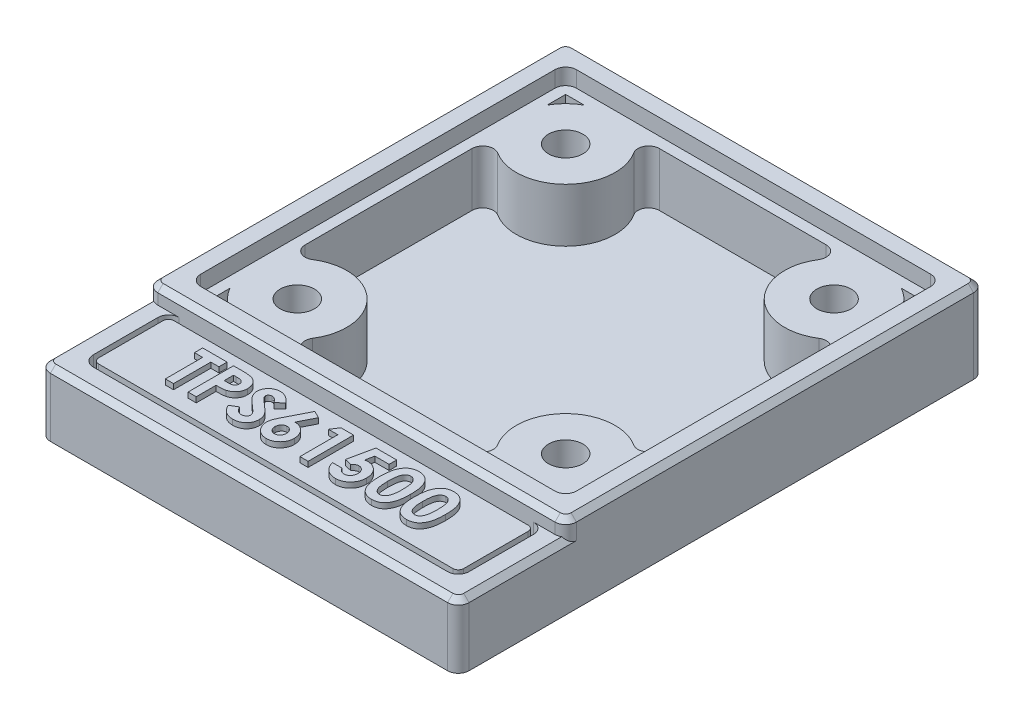
SolidWorks part; units mm, degrees
other "Markup1"
sketch "Sketch7" plane through (-28, 7.5, 62.5) normal (-0.8225, 0.3134, 0.4747) x (0.5688, 0.4607, 0.6813)
material "PET"
ref_plane "Front Plane" through (0, 0, 0) normal (0, 0, 1) x (1, 0, 0)
ref_plane "Top Plane" through (0, 0, 0) normal (0, 1, 0) x (1, 0, 0)
ref_plane "Right Plane" through (0, 0, 0) normal (1, 0, 0) x (0, 0, -1)
sketch "base_sketch" plane through (0, 0, 0) normal (0, 1, 0) x (1, 0, 0)
  line L1 (-12.5, 12.5) -> (12.5, 12.5) construction
  line L2 (-12.5, 12.5) -> (-12.5, -12.5) construction
  line L3 (-12.5, -12.5) -> (12.5, -12.5) construction
  line L4 (12.5, 12.5) -> (12.5, -12.5) construction
  line L5 (-12.5, 12.5) -> (12.5, -12.5) construction
  line L6 (-12.5, -12.5) -> (12.5, 12.5) construction
  line L7 (-17, 17) -> (17, 17) construction
  line L8 (-17, 17) -> (-17, -17) construction
  line L9 (-17, -17) -> (17, -17) construction
  line L10 (17, 17) -> (17, -17) construction
  line L11 (-17, 17) -> (17, -17) construction
  line L12 (-17, -17) -> (17, 17) construction
  circle A0 centre (-12.5, 12.5) radius 1.6 construction
  circle A1 centre (12.5, 12.5) radius 1.6 construction
  circle A2 centre (-12.5, -12.5) radius 1.6 construction
  circle A3 centre (12.5, -12.5) radius 1.6 construction
  point P0 (0, 0)
  point P11 (0, 0)
  dimension "D1" = 3.2
  dimension "D2" = 25
  dimension "D3" = 34
  dimension "D4" = 34
  dimension "D5" = 25
sketch "Sketch3" plane through (0, 0, 0) normal (0, 1, 0) x (1, 0, 0)
  line L14 (-16.5, -16.5) -> (16.5, -16.5)
  line L15 (16.5, -16.5) -> (16.5, 16.5)
  line L16 (16.5, 16.5) -> (-16.5, 16.5)
  line L17 (-16.5, 16.5) -> (-16.5, -16.5)
  line L18 (-16.5, -16.5) -> (16.5, -16.5)
  line L19 (16.5, -16.5) -> (16.5, 16.5)
  line L20 (16.5, 16.5) -> (-16.5, 16.5)
  line L21 (-16.5, 16.5) -> (-16.5, -16.5)
  line L28 (-19.5, 19.5) -> (-19.5, -19.5)
  line L29 (-19.5, -19.5) -> (19.5, -19.5)
  line L30 (19.5, -19.5) -> (19.5, 19.5)
  line L31 (19.5, 19.5) -> (-19.5, 19.5)
  line L32 (-17.5, -17.5) -> (17.5, -17.5)
  line L33 (17.5, -17.5) -> (17.5, 17.5)
  line L34 (17.5, 17.5) -> (-17.5, 17.5)
  line L35 (-17.5, 17.5) -> (-17.5, -17.5)
  line L36 (-17.5, -17.5) -> (17.5, -17.5)
  line L37 (17.5, -17.5) -> (17.5, 17.5)
  line L38 (17.5, 17.5) -> (-17.5, 17.5)
  line L39 (-17.5, 17.5) -> (-17.5, -17.5)
  line L40 (-19.5, -19.5) -> (-19.5, -29.5)
  line L41 (-19.5, -29.5) -> (19.5, -29.5)
  line L42 (19.5, -29.5) -> (19.5, -19.5)
  line L43 (-17.5, -19.5) -> (-17.5, -27.5)
  line L44 (-17.5, -27.5) -> (17.5, -27.5)
  line L45 (17.5, -27.5) -> (17.5, -19.5)
  dimension "D4" = 10
  dimension "D1" = 0.5
  dimension "D2" = 0.5
  dimension "D3" = 2
  dimension "D5" = 2
extrude "Boss-Extrude1" add sketch "Sketch3" along normal blind 1 contours L38 L39 L36 L37 L21 L20 L19 L18 | L20 L21 L18 L19 | L30 L31 L28 L29 L39 L38 L37 L36 | L45 L44 L43 L29 L40 L41 L42 | L44 L45 L29 L43 region at (0, 0, 0) region at (0, 0, -18.9485) region at (-18.5, 0, 19.9026) region at (0, 0, 23.5) region at (-17.005, 0, 0)
extrude "Boss-Extrude2" add sketch "Sketch3<3>" along normal blind 5 from surface contours L45 L44 L43 L29 L40 L41 L42 | L30 L31 L28 L29 L39 L38 L37 L36 | L38 L39 L36 L37 L21 L20 L19 L18 region at (0, 0, -18.9485) region at (-18.5, 0, 19.9026) region at (-17.005, 0, 0) starting at face at (0, 1, 5)
sketch "Sketch3<3>" plane through (0, 0, 0) normal (0, 1, 0) x (1, 0, 0) same geometry as "Sketch3"
extrude "Boss-Extrude3" add sketch "Sketch3<4>" along normal blind 1.5 from surface contours L30 L31 L28 L29 L39 L38 L37 L36 region at (0, 0, -18.9485) starting at face at (0, 6, 0)
sketch "Sketch3<4>" plane through (0, 0, 0) normal (0, 1, 0) x (1, 0, 0) same geometry as "Sketch3"
sketch "Sketch4" plane through (0, 1, 0) normal (0, 1, 0) x (1, 0, 0)
  line L4 (16.5, 16.5) -> (-16.5, 16.5)
  line L5 (-16.5, 16.5) -> (-16.5, -16.5)
  line L6 (-16.5, -16.5) -> (16.5, -16.5)
  line L7 (16.5, -16.5) -> (16.5, 16.5)
  line L8 (16.5, 16.5) -> (-16.5, 16.5)
  line L9 (-16.5, 16.5) -> (-16.5, -16.5)
  line L10 (-16.5, -16.5) -> (16.5, -16.5)
  line L11 (16.5, -16.5) -> (16.5, 16.5)
  circle A0 centre (-12.5, -12.5) radius 1.6 construction
  circle A1 centre (12.5, -12.5) radius 1.6 construction
  circle A2 centre (12.5, 12.5) radius 1.6 construction
  circle A3 centre (-12.5, 12.5) radius 1.6 construction
  circle A4 centre (-12.5, -12.5) radius 1.6
  circle A5 centre (12.5, -12.5) radius 1.6
  circle A6 centre (12.5, 12.5) radius 1.6
  circle A7 centre (-12.5, 12.5) radius 1.6
  circle A8 centre (-12.5, 12.5) radius 4.6
  circle A9 centre (12.5, 12.5) radius 4.6
  circle A10 centre (12.5, -12.5) radius 4.6
  circle A11 centre (-12.5, -12.5) radius 4.6
  dimension "D1" = 0
  dimension "D2" = 3
extrude "Boss-Extrude4" add sketch "Sketch4" along normal up to surface (5 mm away) contours L8 A8 L9 A7 | L11 A9 L8 A6 | L10 A10 L11 A5 | L10 A11 L9 A4 region at (15.6667, 1, -15.6667) region at (-8.6296, 1, -14.753) region at (16.3784, 1, 12.5) region at (-12.5, 1, 16.3784) up to face at (0, 6, 0)
fillet "Fillet1" radius 1 22 edges at (-17.5, 3.5, 27.5) (17.5, 3.5, 27.5) (17.5, 3.5, 19.5) (19.5, 3, 29.5) (-19.5, 3, 29.5) (-17.5, 3.5, 19.5) (-10.2284, 3.5, 16.5) (10.2284, 3.5, 16.5) (16.5, 3.5, 10.2284) (10.2284, 3.5, -16.5) (-10.2284, 3.5, -16.5) (-16.5, 3.5, 10.2284) (16.5, 3.5, -10.2284) (-17.5, 6.75, 17.5) (17.5, 6.75, 17.5) (17.5, 6.75, -17.5) (19.5, 6.75, 19.5) (-19.5, 6.75, 19.5) (-19.5, 3.75, -19.5) (19.5, 3.75, -19.5) (-17.5, 6.75, -17.5) (-16.5, 3.5, -10.2284)
chamfer "Chamfer1" distance 0.5 angle 45 13 edges at (-19.5, 7.5, 0) (-19.2071, 7.5, 19.2071) (-19.2071, 7.5, -19.2071) (0, 7.5, 19.5) (0, 7.5, -19.5) (19.2071, 7.5, 19.2071) (19.2071, 7.5, -19.2071) (19.5, 7.5, 0) (-19.5, 6, 23.5) (-19.2071, 6, 29.2071) (0, 6, 29.5) (19.2071, 6, 29.2071) (19.5, 6, 23.5)
sketch "Sketch5" plane through (0, 1, 0) normal (0, 1, 0) x (1, 0, 0)
  line L0 (-17, -20.5) -> (-17, -26.5)
  line L1 (-16.5, -27) -> (16.5, -27)
  line L2 (17, -26.5) -> (17, -20.5)
  line L3 (16.5, -20) -> (-16.5, -20)
  line L4 (-17.5, -20.5) -> (-17.5, -26.5)
  line L5 (-16.5, -27.5) -> (16.5, -27.5)
  line L6 (17.5, -26.5) -> (17.5, -20.5)
  line L7 (16.5, -19.5) -> (-16.5, -19.5)
  line L8 (-17.5, -20.5) -> (-17.5, -26.5) construction
  line L9 (-16.5, -27.5) -> (16.5, -27.5) construction
  line L10 (17.5, -26.5) -> (17.5, -20.5) construction
  line L11 (16.5, -19.5) -> (-16.5, -19.5) construction
  arc A0 (-17, -26.5) -> (-16.5, -27) centre (-16.5, -26.5) ccw
  arc A1 (16.5, -27) -> (17, -26.5) centre (16.5, -26.5) ccw
  arc A2 (17, -20.5) -> (16.5, -20) centre (16.5, -20.5) ccw
  arc A3 (-16.5, -20) -> (-17, -20.5) centre (-16.5, -20.5) ccw
  arc A4 (-17.5, -26.5) -> (-16.5, -27.5) centre (-16.5, -26.5) ccw
  arc A5 (16.5, -27.5) -> (17.5, -26.5) centre (16.5, -26.5) ccw
  arc A6 (17.5, -20.5) -> (16.5, -19.5) centre (16.5, -20.5) ccw
  arc A7 (-16.5, -19.5) -> (-17.5, -20.5) centre (-16.5, -20.5) ccw
  arc A8 (-17.5, -26.5) -> (-16.5, -27.5) centre (-16.5, -26.5) ccw construction
  arc A9 (16.5, -27.5) -> (17.5, -26.5) centre (16.5, -26.5) ccw construction
  arc A10 (17.5, -20.5) -> (16.5, -19.5) centre (16.5, -20.5) ccw construction
  arc A11 (-16.5, -19.5) -> (-17.5, -20.5) centre (-16.5, -20.5) ccw construction
  dimension "D1" = 0
  dimension "D2" = 0.5
extrude "Boss-Extrude5" add sketch "Sketch5" along normal up to surface (5 mm away) from offset 0.5 separate body up to face at (0, 6, 23.8128)
sketch "Sketch6" plane through (0, 6, 0) normal (0, 1, 0) x (1, 0, 0)
  line L0 (-17, -23.5) -> (17, -23.5) construction
  line L1 (-17, -26.5) -> (-17, -20.5) construction
  line L2 (17, -20.5) -> (17, -26.5) construction
  line L3 (0, -20) -> (0, -27) construction
  line L4 (-16.5, -20) -> (16.5, -20) construction
  line L5 (16.5, -27) -> (-16.5, -27) construction
  line L6 (-17, -25.5959) -> (17, -25.5959) construction
  text T0 "TPS61500" font "Century Gothic" height in points 16
  point P12 (0, -23.5)
  point P15 (-17, -25.5959)
extrude "Boss-Extrude6" add sketch "Sketch6" along normal blind 0.5
